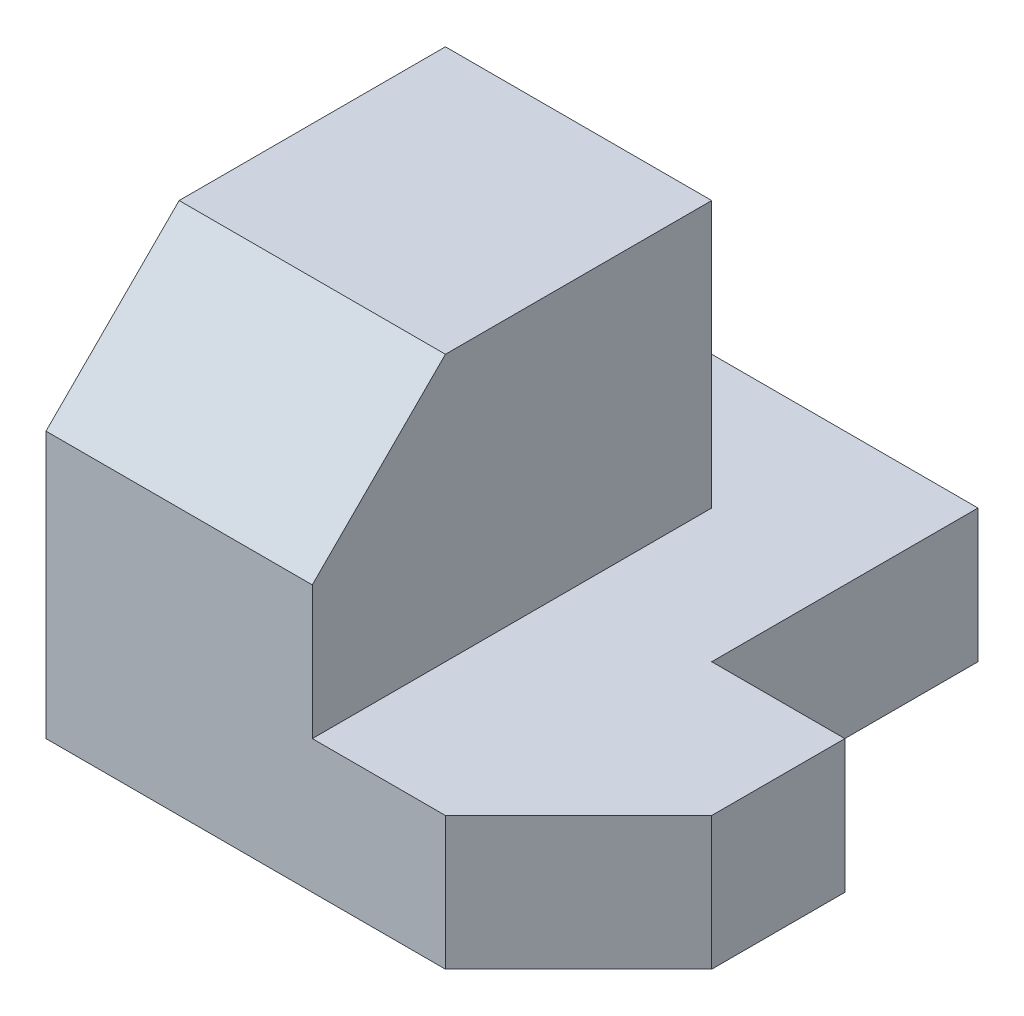
SolidWorks part; units mm, degrees
ref_plane "前基準面" through (0, 0, 0) normal (0, 0, 1) x (1, 0, 0)
ref_plane "上基準面" through (0, 0, 0) normal (0, 1, 0) x (1, 0, 0)
ref_plane "右基準面" through (0, 0, 0) normal (1, 0, 0) x (0, 0, -1)
sketch "草圖1" plane through (0, 0, 0) normal (0, 1, 0) x (1, 0, 0)
  line L0 (0, 0) -> (0, 21.6237) construction
  line L1 (0, 0) -> (0, 4)
  line L2 (0, 4) -> (3, 4)
  line L3 (3, 4) -> (3, 2)
  line L4 (3, 2) -> (4, 2)
  line L5 (4, 2) -> (4, 1)
  line L6 (4, 1) -> (3, 0)
  line L7 (3, 0) -> (0, 0)
  line L8 (0, 3) -> (2, 3)
  line L9 (2, 3) -> (2, 0)
  line L10 (2, 0) -> (2, 1)
  line L11 (2, 1) -> (0, 1)
  point P10 (3.5, 2)
  dimension "D1" = 4
  dimension "D2" = 3
  dimension "D3" = 4
  dimension "D4" = 1
  dimension "D5" = 2
  dimension "D6" = 3
  dimension "D7" = 3
  dimension "D8" = 2
  dimension "D9" = 1
extrude "填料-伸長1" add sketch "草圖1" along normal blind 1 contours L8 L9 L7 L6 L5 L4 L3 L2 L1 | L11 L9 L8 L1 | L9 L11 L1 L7 region at (1, 0, -0.5) region at (1, 0, -2) region at (2.2889, 0, -2.2444)
extrude "填料-伸長2" add sketch "草圖1<3>" along normal blind 3 contours L11 L9 L8 L1 | L9 L11 L1 L7 region at (1, 0, -0.5) region at (1, 0, -2)
sketch "草圖1<3>" plane through (0, 0, 0) normal (0, 1, 0) x (1, 0, 0) same geometry as "草圖1"
sketch "草圖2" plane through (2, 0, 0) normal (1, 0, 0) x (0, 0, -1)
  line L0 (0, 3) -> (0, 2)
  line L1 (0, 3) -> (0, 1) construction
  line L2 (0, 2) -> (1, 3)
  line L3 (3, 3) -> (0, 3) construction
  line L4 (1, 3) -> (0, 3)
  dimension "D1" = 1
  dimension "D2" = 1
extrude "除料-伸長1" cut sketch "草圖2" against normal blind 3
